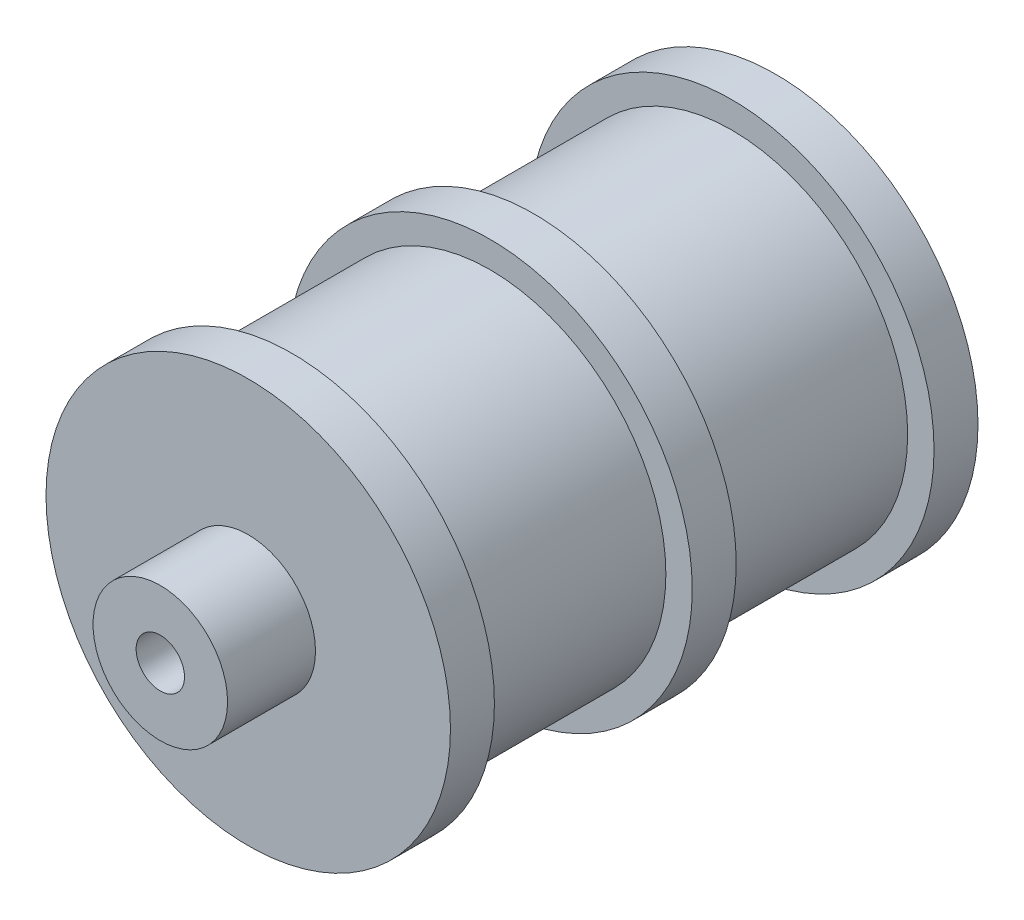
SolidWorks part; units mm, degrees
ref_plane "Front Plane" through (0, 0, 0) normal (0, 0, 1) x (1, 0, 0)
ref_plane "Top Plane" through (0, 0, 0) normal (0, 1, 0) x (1, 0, 0)
ref_plane "Right Plane" through (0, 0, 0) normal (1, 0, 0) x (0, 0, -1)
sketch "Sketch1" plane through (0, 0, 0) normal (0, 0, 1) x (1, 0, 0)
  circle A0 centre (0, 0) radius 23
  dimension "D1" = 46
extrude "Boss-Extrude1" add sketch "Sketch1" along normal blind 2.5 and the other way blind 2.5 contours A0
sketch "Sketch3" plane through (0, 0, 0) normal (0, 0, 1) x (1, 0, 0)
  circle A0 centre (0, 0) radius 20
  dimension "D1" = 40
extrude "Boss-Extrude2" add sketch "Sketch3" along normal blind 30 and the other way blind 30
sketch "Sketch4" plane through (0, 0, 30) normal (0, 0, 1) x (1, 0, 0)
  circle A0 centre (0, 0) radius 23 construction
  circle A1 centre (0, 0) radius 20
  circle A2 centre (0, 0) radius 20
  circle A3 centre (0, 0) radius 23
  dimension "D1" = 0
extrude "Boss-Extrude3" add sketch "Sketch4" against normal blind 5
mirror "Mirror5" about plane through (0, 0, 0) normal (0, 0, 1) of "Boss-Extrude3"
sketch "Sketch5" plane through (0, 0, 30) normal (0, 0, 1) x (1, 0, 0)
  circle A0 centre (0, 0) radius 2.75
  dimension "D1" = 5.5
extrude "Cut-Extrude1" cut sketch "Sketch5" against normal through all
sketch "Sketch6" plane through (0, 0, 30) normal (0, 0, 1) x (1, 0, 0)
  circle A0 centre (0, 0) radius 7.65
  circle A1 centre (0, 0) radius 2.75 construction
  circle A2 centre (0, 0) radius 2.75
  dimension "D1" = 15.3
extrude "Boss-Extrude4" add sketch "Sketch6" along normal blind 10 separate body
